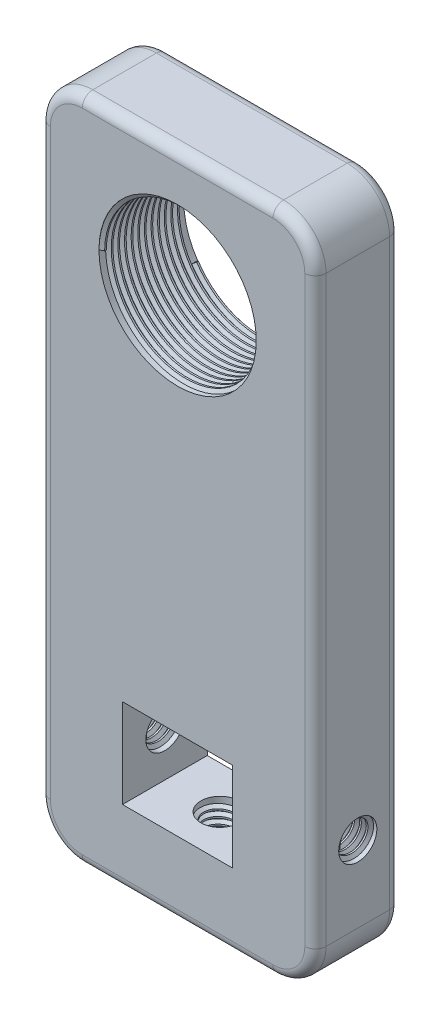
SolidWorks part; units mm, degrees
ref_plane "Front Plane" through (0, 0, 0) normal (0, 0, 1) x (1, 0, 0)
ref_plane "Top Plane" through (0, 0, 0) normal (0, 1, 0) x (1, 0, 0)
ref_plane "Right Plane" through (0, 0, 0) normal (1, 0, 0) x (0, 0, -1)
sketch "Sketch1" plane through (0, 0, 0) normal (0, 0, 1) x (1, 0, 0)
  line L2 (0, 0) -> (0, 66.04)
  line L3 (5.08, 71.12) -> (27.94, 71.12)
  line L4 (33.02, 0) -> (33.02, 66.04)
  line L5 (9.906, 0) -> (9.906, 10.668)
  line L6 (9.906, 10.668) -> (23.114, 10.668)
  line L7 (23.114, 10.668) -> (23.114, 0)
  line L11 (0, 0) -> (0, -3.81)
  line L12 (5.08, -8.89) -> (27.94, -8.89)
  line L13 (33.02, -3.81) -> (33.02, 0)
  line L14 (9.906, 0) -> (23.114, 0)
  line L15 (16.51, 71.12) -> (16.51, 56.134) construction
  line L16 (16.51, 56.134) -> (16.51, 25.654) construction
  line L17 (16.51, 10.668) -> (16.51, 25.654) construction
  line L18 (16.51, 0) -> (16.51, -8.89) construction
  line L19 (0, 10.668) -> (33.02, 10.668) construction
  arc A3 (0, -3.81) -> (5.08, -8.89) centre (5.08, -3.81) ccw
  arc A4 (27.94, -8.89) -> (33.02, -3.81) centre (27.94, -3.81) ccw
  arc A5 (27.94, 71.12) -> (33.02, 66.04) centre (27.94, 66.04) cw
  arc A6 (0, 66.04) -> (5.08, 71.12) centre (5.08, 66.04) cw
  circle A8 centre (16.51, 56.134) radius 9.4234
  point P16 (16.51, 71.12)
  point P27 (0, 71.12)
  dimension "D5" = 18.8468
  dimension "D7" = 5.08
  dimension "D6" = 9.906
  dimension "D1" = 13.208
  dimension "D2" = 71.12
  dimension "D3" = 10.668
  dimension "D4" = 8.89
extrude "Boss-Extrude2" add sketch "Sketch1" along normal blind 10.16
sketch "Sketch4" plane through (0, 0, 0) normal (-1, 0, 0) x (0, 0, 1)
  circle A0 centre (5.08, 5.334) radius 2.286
  dimension "D1" = 4.572
  dimension "D2" = 5.334
extrude "Cut-Extrude1" cut sketch "Sketch4" against normal blind 38.1
sketch "Sketch6" plane through (0, -8.89, 0) normal (0, -1, 0) x (1, 0, 0)
  line L0 (16.51, 5.08) -> (16.51, 10.16) construction
  line L1 (5.08, 10.16) -> (27.94, 10.16) construction
  line L2 (16.51, 5.08) -> (27.94, 5.08) construction
  line L3 (27.94, 10.16) -> (27.94, 0) construction
  circle A0 centre (16.51, 5.08) radius 2.286
  dimension "D1" = 4.572
extrude "Cut-Extrude2" cut sketch "Sketch6" against normal blind 10.16
thread "Thread1" pitch 0.7937 method extrude profile "Thread Profile1" start angle 0, offset 0, length 9.4488, pitch 0.7937, diameter 18.8468
ref_plane "Plane1" through (7.0866, 56.134, 10.16) normal (0, -1, 0) x (-1, 0, 0)
sketch "Thread Profile1" plane through (7.0866, 56.134, 10.16) normal (0, -1, 0) x (-1, 0, 0)
  line L0 (0, 0) -> (0, 0.7937) construction
  line L11 (0, 0) -> (0, 0.6945)
  line L12 (0, 0.6945) -> (-0.4296, 0.4465)
  line L13 (-0.4296, 0.4465) -> (-0.4296, 0.248)
  line L15 (-0.4296, 0.248) -> (0, 0)
  line L17 (-0.4296, 0.3473) -> (0, 0.3473) construction
  point P2 (0, 0)
  dimension "Pitch" = 0.7937
  dimension "Profile_Angle" = 60
  dimension "Profile_Land" = 0.1984
  dimension "Profile_Height" = 0.4296
thread "Thread2" pitch 0.7937 method extrude profile "Thread Profile2" start angle 0, offset 0, length 9.144, pitch 0.7937, diameter 4.572
ref_plane "Plane2" through (0, 5.334, 2.794) normal (0, -1, 0) x (0, 0, -1)
sketch "Thread Profile2" plane through (0, 5.334, 2.794) normal (0, -1, 0) x (0, 0, -1)
  line L0 (0, 0) -> (0, 0.7937) construction
  line L11 (0, 0) -> (0, 0.6945)
  line L12 (0, 0.6945) -> (-0.4296, 0.4465)
  line L13 (-0.4296, 0.4465) -> (-0.4296, 0.248)
  line L15 (-0.4296, 0.248) -> (0, 0)
  line L17 (-0.4296, 0.3473) -> (0, 0.3473) construction
  point P2 (0, 0)
  dimension "Pitch" = 0.7937
  dimension "Profile_Angle" = 60
  dimension "Profile_Land" = 0.1984
  dimension "Profile_Height" = 0.4296
thread "Thread3" pitch 0.7937 method extrude profile "Thread Profile3" start angle 0, offset 0, length 9.144, pitch 0.7937, diameter 4.572
ref_plane "Plane3" through (33.02, 5.334, 7.366) normal (0, -1, 0) x (0, 0, 1)
sketch "Thread Profile3" plane through (33.02, 5.334, 7.366) normal (0, -1, 0) x (0, 0, 1)
  line L0 (0, 0) -> (0, 0.7937) construction
  line L11 (0, 0) -> (0, 0.6945)
  line L12 (0, 0.6945) -> (-0.4296, 0.4465)
  line L13 (-0.4296, 0.4465) -> (-0.4296, 0.248)
  line L15 (-0.4296, 0.248) -> (0, 0)
  line L17 (-0.4296, 0.3473) -> (0, 0.3473) construction
  point P2 (0, 0)
  dimension "Pitch" = 0.7937
  dimension "Profile_Angle" = 60
  dimension "Profile_Land" = 0.1984
  dimension "Profile_Height" = 0.4296
thread "Thread4" pitch 0.7937 method extrude profile "Thread Profile4" start angle 0, offset 0, length 8.128, pitch 0.7937, diameter 4.572
ref_plane "Plane4" through (18.796, -8.89, 5.08) normal (0, 0, 1) x (1, 0, 0)
sketch "Thread Profile4" plane through (18.796, -8.89, 5.08) normal (0, 0, 1) x (1, 0, 0)
  line L0 (0, 0) -> (0, 0.7937) construction
  line L11 (0, 0) -> (0, 0.6945)
  line L12 (0, 0.6945) -> (-0.4296, 0.4465)
  line L13 (-0.4296, 0.4465) -> (-0.4296, 0.248)
  line L15 (-0.4296, 0.248) -> (0, 0)
  line L17 (-0.4296, 0.3473) -> (0, 0.3473) construction
  point P2 (0, 0)
  dimension "Pitch" = 0.7937
  dimension "Profile_Angle" = 60
  dimension "Profile_Land" = 0.1984
  dimension "Profile_Height" = 0.4296
fillet "Fillet1" radius 1.27 16 edges at (1.4879, 69.6321, 10.16) (0, 31.115, 10.16) (1.4879, -7.4021, 10.16) (16.51, -8.89, 10.16) (31.5321, -7.4021, 10.16) (33.02, 31.115, 10.16) (31.5321, 69.6321, 10.16) (16.51, 71.12, 10.16) (1.4879, 69.6321, 0) (31.5321, 69.6321, 0) (16.51, 71.12, 0) (0, 31.115, 0) (31.5321, -7.4021, 0) (33.02, 31.115, 0) (1.4879, -7.4021, 0) (16.51, -8.89, 0)
